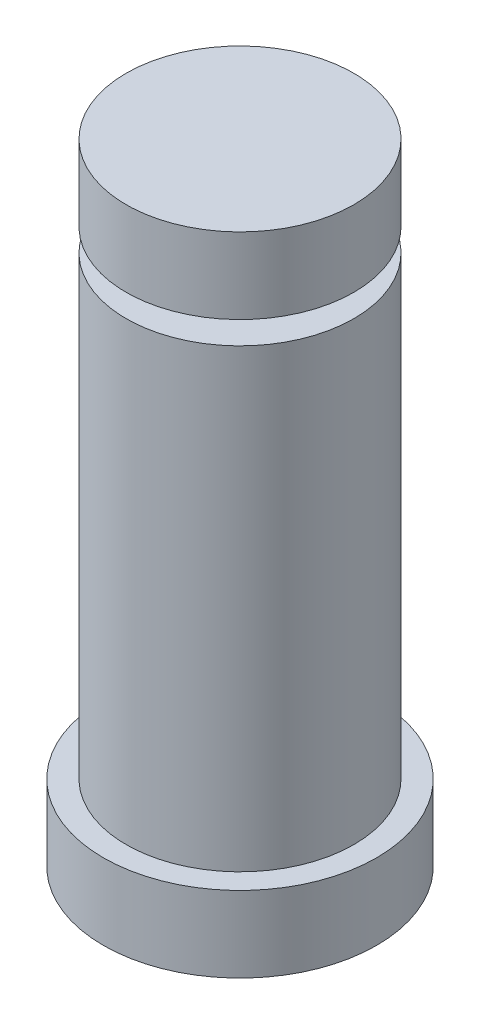
SolidWorks part; units mm, degrees
material "K110"
ref_plane "Front Plane" through (0, 0, 0) normal (0, 0, 1) x (1, 0, 0)
ref_plane "Top Plane" through (0, 0, 0) normal (0, 1, 0) x (1, 0, 0)
ref_plane "Right Plane" through (0, 0, 0) normal (1, 0, 0) x (0, 0, -1)
sketch "Sketch1" plane through (0, 0, 0) normal (0, 0, 1) x (1, 0, 0)
  line L0 (0, 0) -> (9, 0)
  line L1 (9, 0) -> (9, 5)
  line L2 (9, 5) -> (7.5, 5)
  line L3 (7.5, 5) -> (7.5, 41.5)
  line L4 (7.5, 41.5) -> (0, 41.5)
  line L5 (0, 41.5) -> (0, 0)
  line L6 (0, 46.5) -> (0, -5) construction
  point P9 (8.25, 5)
  dimension "D1" = 5
  dimension "D2" = 5
  dimension "D3" = 18
  dimension "D4" = 15
  dimension "D5" = 5
  dimension "D6" = 36.5
revolve "Revolve1" add sketch "Sketch1" angle 360 about L6
sketch "Sketch2" plane through (0, 0, 0) normal (0, 0, 1) x (1, 0, 0)
  line L0 (7.5, 5) -> (7.5, 41.5) construction
  line L1 (7.5, 35) -> (4.85, 35)
  line L2 (7.5, 35) -> (7.5, 36.5)
  line L3 (7.5, 36.5) -> (4.85, 36.5)
  line L4 (4.85, 35) -> (4.85, 36.5)
  line L5 (0, 41.5) -> (0, 5) construction
  line L6 (7.5, 41.5) -> (-7.5, 41.5) construction
  line L7 (9, 5) -> (-9, 5) construction
  dimension "D1" = 1.5
  dimension "D2" = 2.65
  dimension "D3" = 30
revolve "Cut-Revolve1" cut sketch "Sketch2" angle 360 about L5
